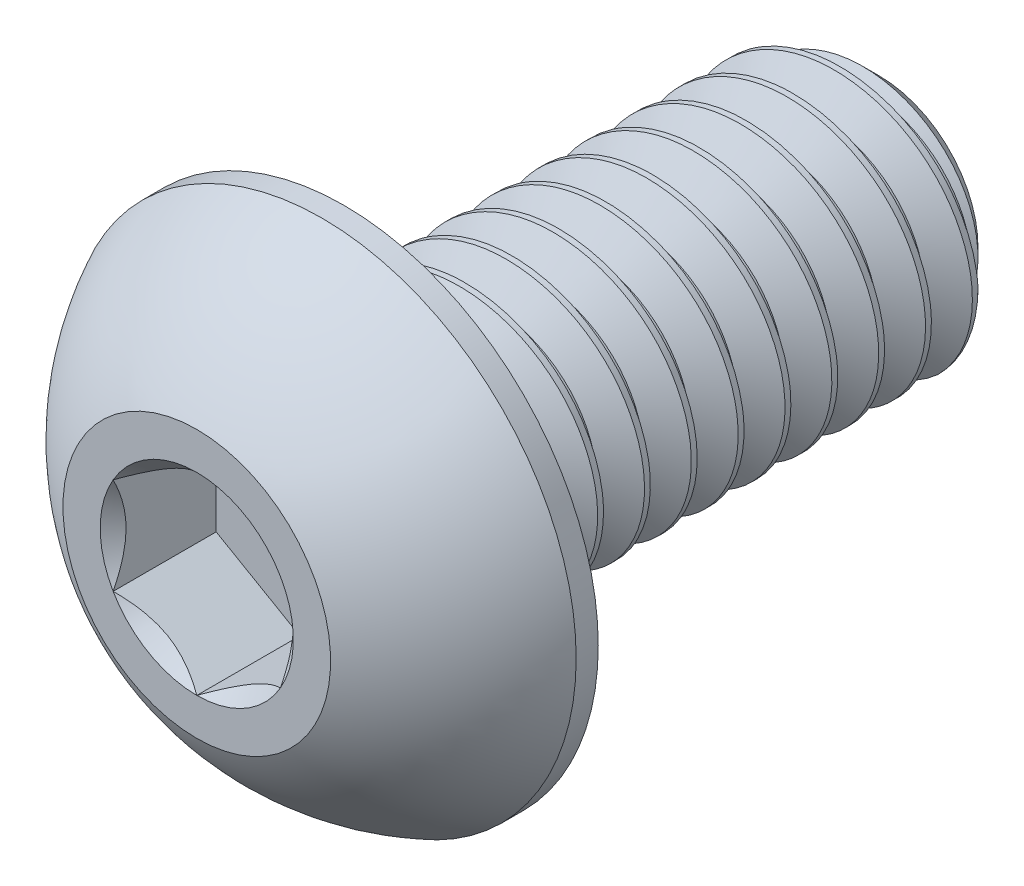
SolidWorks part; units mm, degrees
ref_plane "Front" through (0, 0, 0) normal (0, 0, 1) x (1, 0, 0)
ref_plane "Top" through (0, 0, 0) normal (0, 1, 0) x (1, 0, 0)
ref_plane "Right" through (0, 0, 0) normal (1, 0, 0) x (0, 0, -1)
sketch "Sketch1" plane through (0, 0, 0) normal (1, 0, 0) x (0, 0, -1)
  line L2 (2.2, 2) -> (10.2, 2)
  line L3 (10.2, 2) -> (10.2, 0)
  line L4 (10.2, 0) -> (2.2, 0)
  line L6 (1.87, 3.8) -> (2.2, 3.8) construction
  line L7 (10.2, 2) -> (10.2, -2) construction
  line L8 (0, 0) -> (2.2, 0) construction
  line L9 (2.2, 3.8) -> (2.2, -3.8) construction
  line L11 (2.2, 2) -> (2.2, 0)
  line L13 (0, 1.25) -> (0, -1.25) construction
  line L14 (0, 1.25) -> (0, 2) construction
  arc A3 (0, 2) -> (1.87, 3.8) centre (3.7264, 0) cw construction
  dimension "D1" = 0.33
revolve "Revolve1" add sketch "Sketch1" angle 360 mid plane about L4
sketch "Sketch3" plane through (0, 0, -10.2) normal (0, 0, -1) x (-1, 0, 0)
  circle A0 centre (0, 0) radius 2
curve "Helix/Spiral1" pitch 0.7 height 10.2 radius 2 centre (0, 0, -10.2) axis (0, 0, 1) start towards (0, 1, 0)
sketch "Sketch2" plane through (0, 0, 0) normal (1, 0, 0) x (0, 0, -1)
  line L0 (10.2, 2) -> (10.8125, 2)
  line L1 (10.8125, 2) -> (10.55, 1.5453)
  line L2 (10.55, 1.5453) -> (10.4625, 1.5453)
  line L3 (10.4625, 1.5453) -> (10.2, 2)
  line L4 (10.3313, 1.7727) -> (10.6813, 1.7727) construction
  dimension "D1" = 60
  dimension "D2" = 0.0875
  dimension "D3" = 0.35
chamfer "Chamfer1" distance 0.525 angle 45 1 edges at (0, 2, -10.2)
sweep "Cut-Sweep1" cut profiles "Sketch2" path "Helix/Spiral1" align with end faces yes
sketch "Sketch7" plane through (0, 0, 0) normal (1, 0, 0) x (0, 0, -1)
  line L6 (1.87, 3.8) -> (2.2, 3.8) construction
  line L8 (0, 0) -> (2.2, 0) construction
  line L11 (2.2, 3.8) -> (2.2, -3.8) construction
  line L12 (1.87, 3.8) -> (2.2, 3.8)
  line L13 (0, 0) -> (2.2, 0)
  line L14 (0, 1.25) -> (0, -1.25) construction
  line L15 (2.2, 3.8) -> (2.2, 0)
  line L16 (0, 2) -> (0, 0)
  arc A2 (1.87, 3.8) -> (0, 2) centre (3.7264, 0) ccw construction
  arc A3 (1.87, 3.8) -> (0, 2) centre (3.7264, 0) ccw
revolve "Revolve2" add sketch "Sketch7" angle 360 mid plane about L13
sketch "Sketch5" plane through (0, 0, 0) normal (0, 0, 1) x (1, 0, 0)
  line L1 (1.25, -0.7217) -> (1.25, 0.7217)
  line L2 (1.25, 0.7217) -> (0, 1.4434)
  line L3 (0, 1.4434) -> (-1.25, 0.7217)
  line L4 (-1.25, 0.7217) -> (-1.25, -0.7217)
  line L5 (-1.25, -0.7217) -> (0, -1.4434)
  line L6 (0, -1.4434) -> (1.25, -0.7217)
  circle A0 centre (0, 0) radius 1.25 construction
extrude "Cut-Extrude2" cut sketch "Sketch5" against normal blind 1.54
sketch "Sketch6" plane through (0, 0, 0) normal (0, 0, 1) x (1, 0, 0)
  circle A0 centre (0, 0) radius 1.4434
extrude "Cut-Extrude3" cut sketch "Sketch6" against normal blind 1.54 draft 45
sketch "Sketch9" [suppressed] plane through (0, 0, -2.2) normal (0, 0, 1) x (1, 0, 0)
  circle A2 centre (0, 0) radius 1.5
extrude "Boss-Extrude2" [suppressed] add sketch "Sketch9" against normal offset from surface (20 mm away) 32 up to face at (0, 1.475, -10.2)
sketch "Sketch10" plane through (0, 0, 0) normal (1, 0, 0) x (0, 0, -1)
  line L0 (10.2, 2) -> (10.2, -2) construction
  point P0 (9.15, -2)
  dimension "D1" = 1.05
equation "\"D3@Helix/Spiral1\" = \"Lg@Sketch1\" + \"Head Ht@Sketch1\""
equation "\"D2@Sketch2\" = \"D4@Helix/Spiral1\" * .125"
equation "\"D3@Sketch2\" = \"D4@Helix/Spiral1\" * .5"
equation "\"D1@Chamfer1\" = \"D4@Helix/Spiral1\" * .75"
equation "\"D1@Cut-Extrude2\" = \"Head Ht@Sketch1\" * .7"
equation "\"D1@Sketch1\" = \"Head Ht@Sketch1\" * .15"
equation "\"D1@Sketch10\" = \"D4@Helix/Spiral1\" * 1.5"
equation "\"D1@Cut-Extrude3\" = \"D1@Cut-Extrude2\""
